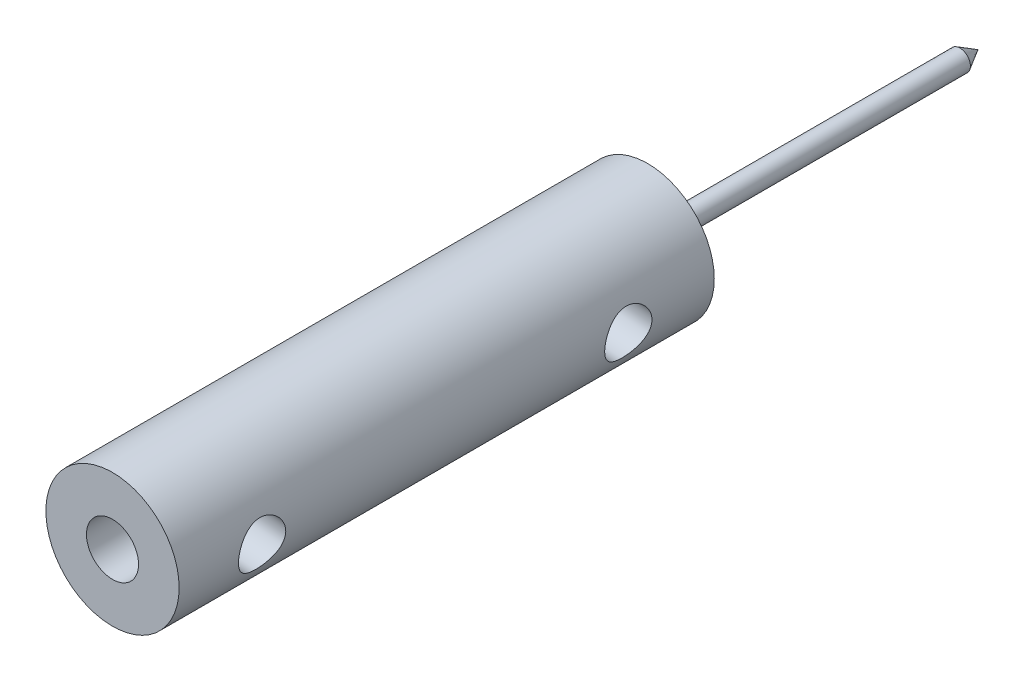
SolidWorks part; units mm, degrees
ref_plane "Front Plane" through (0, 0, 0) normal (0, 0, 1) x (1, 0, 0)
ref_plane "Top Plane" through (0, 0, 0) normal (0, 1, 0) x (1, 0, 0)
ref_plane "Right Plane" through (0, 0, 0) normal (1, 0, 0) x (0, 0, -1)
sketch "Sketch3" plane through (0, 0, 0) normal (0, 0, 1) x (1, 0, 0)
  circle A0 centre (0, 0) radius 3.2
  circle A1 centre (0, 0) radius 0.5
  dimension "D1" = 6.4
  dimension "D2" = 1
extrude "Boss-Extrude2" add sketch "Sketch3" along normal blind 25.7
sketch "Sketch6" plane through (0, 0, 25.7) normal (0, 0, 1) x (1, 0, 0)
  circle A0 centre (0, 0) radius 1.25
  circle M3 centre (0, 0) radius 0.5
  dimension "D1" = 2.5
extrude "Cut-Extrude1" cut sketch "Sketch6" against normal blind 25.7 and the other way through all
hole_wizard "Tap Drill for #4-40 Tap1" positions "3DSketch1" profile "Sketch8" hole size "#4-40" standard "ANSI Inch" end condition through all
sketch3d "3DSketch1"
  line L0 (3.1875, -0.2822, 21.7) -> (3.1875, -0.2822, 4.1124) construction
  point P0 (3.1875, -0.2822, 21.7)
  point P1 (3.1875, -0.2822, 4.1124)
  dimension "D1" = 4
sketch "Sketch8" plane through (3.1875, -0.2822, 21.7) normal (0, 0, 1) x (0.0882, 0.9961, 0)
  line L0 (0, 0) -> (0, 6.6698)
  line L1 (0, 6.6698) -> (1.1303, 6.6698)
  line L2 (1.1303, 6.6698) -> (1.1303, 0)
  line L5 (1.1303, 0) -> (0, 0)
  line L11 (0, -6.35) -> (0, 107.95) construction
  dimension "Thru Hole Dia." = 2.2606
  dimension "Thru Hole Depth" = 6.6698
extrude "Boss-Extrude4" add sketch "Sketch3<4>" against normal blind 20 from offset 5 separate body contours A1 region at (0, 0, 0)
sketch "Sketch3<4>" plane through (0, 0, 0) normal (0, 0, 1) x (1, 0, 0) same geometry as "Sketch3"
sketch "Sketch9" plane through (0, 0, 0) normal (0, 1, 0) x (1, 0, 0)
  line L0 (0, 15) -> (0, 15.866) construction
  line L1 (0, 15) -> (-0.5, 15)
  line L2 (-0.5, 15) -> (0, 15.866)
  line L3 (0.5, 15) -> (-0.5, 15) construction
  line L4 (0, 15) -> (0, 15.866)
  point P3 (0, 0)
  point P6 (0, 10)
  point P7 (0, 0)
  point P8 (0, 0)
  dimension "D1" = 30
revolve "Revolve1" add sketch "Sketch9" angle 360 about L0
extrude "Boss-Extrude5" add sketch "Sketch6<2>" along normal blind 5 from surface contours A0 M3 region at (-1.2146, 0, 25.7) starting at face at (1.25, 0, 0)
sketch "Sketch6<2>" plane through (0, 0, 25.7) normal (0, 0, 1) x (1, 0, 0) same geometry as "Sketch6"
